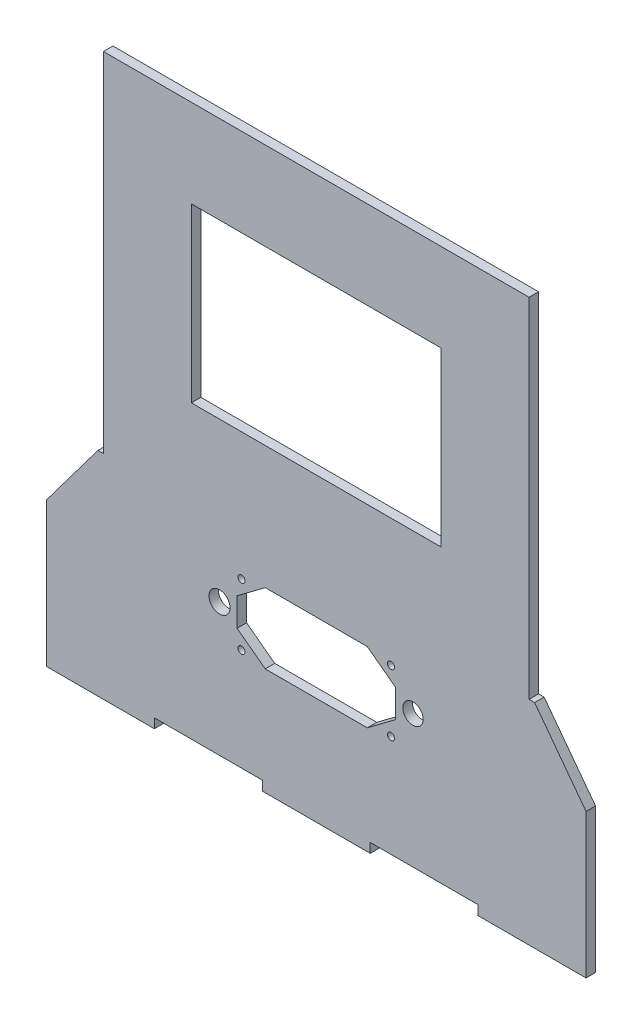
SolidWorks part; units mm, degrees
ref_plane "Ön Düzlem" through (0, 0, 0) normal (0, 0, 1) x (1, 0, 0)
ref_plane "Üst Düzlem" through (0, 0, 0) normal (0, 1, 0) x (1, 0, 0)
ref_plane "Sağ Düzlem" through (0, 0, 0) normal (1, 0, 0) x (0, 0, -1)
sketch "Sketch1" plane through (0, 0, 0) normal (0, 0, 1) x (1, 0, 0)
  line L14 (-76.7, 13) -> (-62.075, 32.5)
  line L15 (62.075, 32.5) -> (76.7, 13)
  line L21 (-46.02, -28) -> (-46.02, -25.3)
  line L22 (-15.34, -28) -> (-15.34, -25.3)
  line L23 (15.34, -28) -> (15.34, -25.3)
  line L24 (46.02, -28) -> (46.02, -25.3)
  line L26 (-76.7, -23) -> (-76.7, 13)
  line L27 (-76.7, -23) -> (-76.7, -25.3)
  line L28 (76.7, -23) -> (76.7, 13)
  line L30 (76.7, -25.3) -> (76.7, -23)
  line L33 (-46.02, -28) -> (-76.7, -28)
  line L34 (-76.7, -28) -> (-76.7, -25.3)
  line L35 (-15.34, -25.3) -> (-46.02, -25.3)
  line L36 (-15.34, -28) -> (15.34, -28)
  line L37 (15.34, -25.3) -> (46.02, -25.3)
  line L38 (46.02, -28) -> (76.7, -28)
  line L39 (76.7, -28) -> (76.7, -25.3)
  line L54 (-60.5, 32.5) -> (-62.075, 32.5)
  line L56 (-22.5, 16.5) -> (-14.5, 22.5)
  line L57 (-14.5, 22.5) -> (14.5, 22.5)
  line L58 (0, 2.5) -> (14.5, 2.5)
  line L59 (-14.5, 2.5) -> (-22.5, 8.5)
  line L60 (-22.5, 8.5) -> (-22.5, 16.5)
  line L61 (14.5, 2.5) -> (22.5, 8.5)
  line L62 (14.5, 22.5) -> (22.5, 16.5)
  line L63 (0, 2.5) -> (-14.5, 2.5)
  line L64 (22.5, 16.5) -> (22.5, 8.5)
  line L65 (35.5, 57.5) -> (-35.5, 57.5)
  line L66 (35.5, 57.5) -> (35.5, 106.5)
  line L67 (35.5, 106.5) -> (-35.5, 106.5)
  line L68 (-35.5, 57.5) -> (-35.5, 106.5)
  line L70 (60.5, 32.5) -> (60.5, 131.5)
  line L71 (60.5, 131.5) -> (-60.5, 131.5)
  line L72 (-60.5, 32.5) -> (-60.5, 131.5)
  line L75 (60.5, 32.5) -> (62.075, 32.5)
  circle A11 centre (-21.25, 3.75) radius 1
  circle A12 centre (-27.5, 12.5) radius 3
  circle A13 centre (-21.25, 21.25) radius 1
  circle A14 centre (21.25, 3.75) radius 1
  circle A15 centre (27.5, 12.5) radius 2.9
  circle A16 centre (21.25, 21.25) radius 1
  point P0 (0, 82)
  point P6 (76.7, 33)
  point P7 (-76.7, 33)
  dimension "D4" = 20
  dimension "D6" = 20
extrude "Boss-Extrude3" add sketch "Sketch1" along normal blind 2.7
